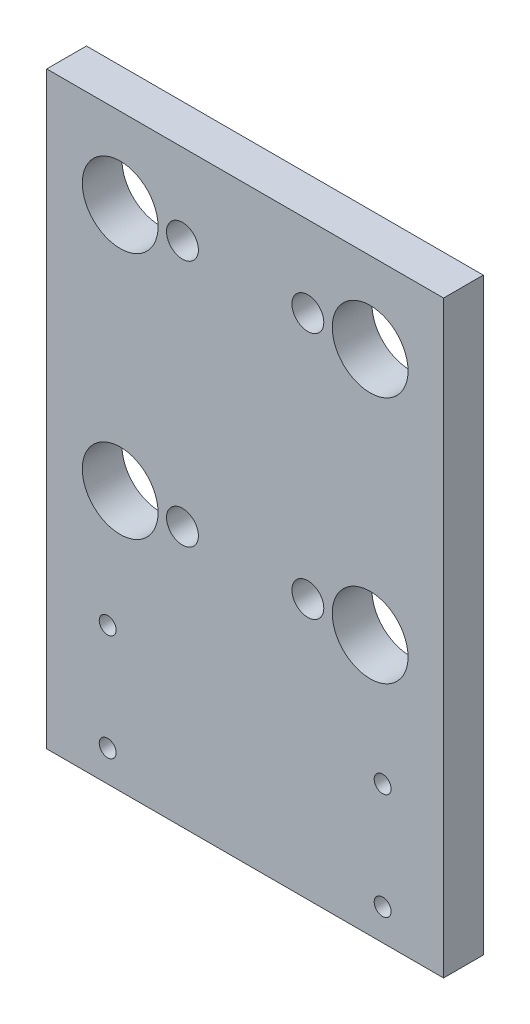
SolidWorks part; units mm, degrees
material "PLA White"
ref_plane "Front Plane" through (0, 0, 0) normal (0, 0, 1) x (1, 0, 0)
ref_plane "Top Plane" through (0, 0, 0) normal (0, 1, 0) x (1, 0, 0)
ref_plane "Right Plane" through (0, 0, 0) normal (1, 0, 0) x (0, 0, -1)
sketch "Sketch1" plane through (0, 0, 0) normal (1, 0, 0) x (0, 0, -1)
  line L2 (0, -47.117) -> (0, 47.117)
  line L4 (6.35, -47.117) -> (6.35, 47.117)
  line L15 (6.35, -47.117) -> (0, -47.117)
  line L24 (6.35, 47.117) -> (0, 47.117)
  point P14 (0, 0)
  dimension "D3" = 6.35
  dimension "D4" = 94.234
extrude "Boss-Extrude1" add sketch "Sketch1" along normal mid plane 63.5
sketch "Sketch15" plane through (0, 0, 0) normal (0, 0, 1) x (1, 0, 0)
  line L0 (-20, 34.163) -> (20, 34.163) construction
  line L1 (20, 34.163) -> (20, -5.461) construction
  line L2 (20, -5.461) -> (-20, -5.461) construction
  line L3 (-20, -5.461) -> (-20, 34.163) construction
  line L4 (-20, 34.163) -> (20, -5.461) construction
  line L5 (20, 14.351) -> (-20, 14.351) construction
  line L7 (-10.033, 34.163) -> (-10.033, -5.461) construction
  line L8 (10.033, -5.461) -> (10.033, 34.163) construction
  line L9 (-10.033, 31.4894) -> (10.033, 31.4894) construction
  line L10 (31.75, 47.117) -> (-31.75, 47.117) construction
  circle A8 centre (-20, -5.461) radius 2 construction
  circle A9 centre (20, -5.461) radius 2 construction
  circle A10 centre (20, 34.163) radius 2 construction
  circle A11 centre (-20, 34.163) radius 2 construction
  circle A12 centre (10.033, 34.163) radius 2.55
  arc A13 (11.1958, -7.7305) -> (9.2611, -7.8914) centre (10.033, -5.461) ccw
  circle A14 centre (-10.033, -5.461) radius 2.55
  arc A15 (-12.2219, 32.8548) -> (-7.8441, 32.8548) centre (-10.033, 34.163) ccw
  circle A16 centre (-10.033, 34.163) radius 2.55
  circle A17 centre (10.033, -5.461) radius 2.55
  circle A18 centre (-20, 34.163) radius 6.064
  circle A19 centre (20, 34.163) radius 6.064
  circle A20 centre (20, -5.461) radius 6.064
  circle A21 centre (-20, -5.461) radius 6.064
  point P1 (0, 14.351)
  point P9 (0, 14.351)
  point P37 (0, 31.4894)
  point P38 (0, 0)
  point P39 (0, 0)
  point P40 (-10, -0.7821)
  point P41 (10, -0.7821)
  dimension "D5" = 5.1
  dimension "D6" = 4
  dimension "D2" = 12.954
  dimension "D3" = 39.624
  dimension "D4" = 40
  dimension "D7" = 20.066
  dimension "D1" = 4.064
extrude "Cut-Extrude8" cut sketch "Sketch15" against normal through all contours A11 | A15 A16 | A12 | A10 | A13 A17 | A9 | A14 | A8 | A18 | A21 | A20 | A19 region at (10.033, 34.163, 0) region at (10.033, -5.461, 0) region at (-10.033, -5.461, 0) region at (-10.033, 34.163, 0) region at (-20, 34.163, 0) region at (20, 34.163, 0) region at (20, -5.461, 0) region at (-20, -5.461, 0)
sketch "Sketch16" plane through (0, 0, -6.35) normal (0, 0, -1) x (-1, 0, 0)
  line L0 (-31.75, -47.117) -> (31.75, -47.117) construction
  line L1 (-22, -42.117) -> (22, -42.117) construction
  line L2 (-22, -42.117) -> (-22, -25.099) construction
  line L3 (-22, -25.099) -> (22, -25.099) construction
  line L4 (22, -42.117) -> (22, -25.099) construction
  line L5 (-22, -42.117) -> (22, -25.099) construction
  line L6 (-22, -25.099) -> (22, -42.117) construction
  circle A4 centre (-22, -25.099) radius 1.3525
  circle A5 centre (22, -25.099) radius 1.3525
  circle A6 centre (22, -42.117) radius 1.3526
  circle A7 centre (-22, -42.117) radius 1.3526
  point P8 (0, -33.608)
  dimension "D1" = 2.7051
  dimension "D4" = 17.018
  dimension "D2" = 44
  dimension "D3" = 5
extrude "Cut-Extrude9" cut sketch "Sketch16" against normal through all
sketch "Sketch17" plane through (0, 0, -6.35) normal (0, 0, -1) x (-1, 0, 0)
  line L0 (-27.08, -42.117) -> (-27.08, -47.117)
  line L1 (-31.75, -47.117) -> (31.75, -47.117) construction
  line L2 (-27.08, -47.117) -> (-16.92, -47.117)
  line L3 (-16.92, -47.117) -> (-16.92, -42.117)
  line L4 (16.92, -42.117) -> (16.92, -47.117)
  line L5 (16.92, -47.117) -> (27.08, -47.117)
  line L6 (27.08, -47.117) -> (27.08, -42.117)
  circle A0 centre (-22, -25.099) radius 5.08
  circle A3 centre (22, -25.099) radius 5.08
  arc A4 (-16.92, -42.117) -> (-27.08, -42.117) centre (-22, -42.117) ccw
  arc A5 (27.08, -42.117) -> (16.92, -42.117) centre (22, -42.117) ccw
  dimension "D1" = 10.16
extrude "Cut-Extrude10" cut sketch "Sketch17" against normal blind 2.032
